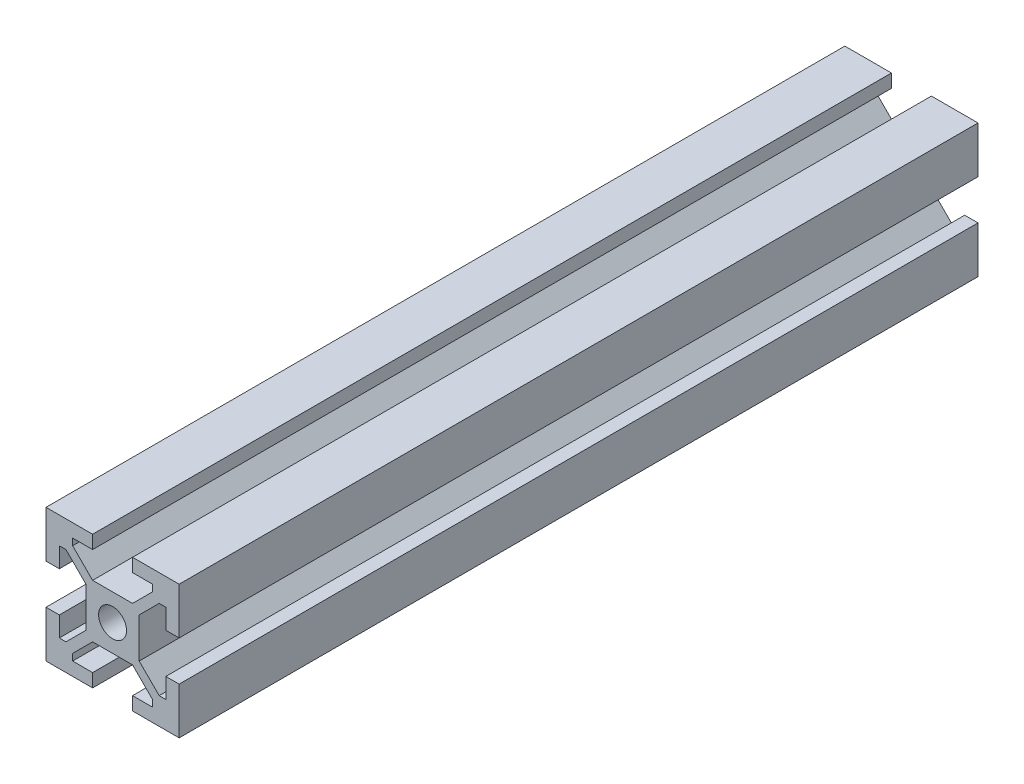
SolidWorks part; units mm, degrees
ref_plane "正面" through (0, 0, 0) normal (0, 0, 1) x (1, 0, 0)
ref_plane "平面" through (0, 0, 0) normal (0, 1, 0) x (1, 0, 0)
ref_plane "右側面" through (0, 0, 0) normal (1, 0, 0) x (0, 0, -1)
sketch "ｽｹｯﾁ2" plane through (0, 0, 0) normal (0, 0, 1) x (1, 0, 0)
  line L0 (0, 0) -> (0, 10) construction
  line L1 (-10, -10) -> (10, -10) construction
  line L2 (-10, -10) -> (-10, 10) construction
  line L3 (-10, 10) -> (10, 10) construction
  line L4 (10, -10) -> (10, 10) construction
  line L5 (-10, -10) -> (10, 10) construction
  line L6 (-10, 10) -> (10, -10) construction
  line L8 (3, 4) -> (-3, 4)
  line L9 (-6, 7) -> (6, 7) construction
  line L10 (-6, 8) -> (-6, 7)
  line L11 (6, 8) -> (6, 7)
  line L12 (-6, 7) -> (-3, 4)
  line L13 (3, 4) -> (6, 7)
  line L14 (-6, 8) -> (-3, 8)
  line L15 (-3, 8) -> (-3, 10)
  line L16 (-3, 10) -> (-10, 10)
  line L17 (6, 8) -> (3, 8)
  line L18 (3, 8) -> (3, 10)
  line L19 (3, 10) -> (10, 10)
  line L20 (7, 6) -> (4, 3)
  line L21 (4, -3) -> (4, 3)
  line L22 (4, -3) -> (7, -6)
  line L23 (8, -6) -> (8, -3)
  line L24 (8, -6) -> (7, -6)
  line L25 (8, -3) -> (10, -3)
  line L26 (10, -3) -> (10, -10)
  line L27 (8, 3) -> (10, 3)
  line L28 (10, 3) -> (10, 10)
  line L29 (8, 6) -> (8, 3)
  line L30 (8, 6) -> (7, 6)
  line L31 (6, -7) -> (3, -4)
  line L32 (-3, -4) -> (3, -4)
  line L33 (-3, -4) -> (-6, -7)
  line L34 (-6, -8) -> (-3, -8)
  line L35 (-6, -8) -> (-6, -7)
  line L36 (-3, -8) -> (-3, -10)
  line L37 (-3, -10) -> (-10, -10)
  line L38 (3, -8) -> (3, -10)
  line L39 (3, -10) -> (10, -10)
  line L40 (6, -8) -> (3, -8)
  line L41 (6, -8) -> (6, -7)
  line L42 (-7, -6) -> (-4, -3)
  line L43 (-4, 3) -> (-4, -3)
  line L44 (-4, 3) -> (-7, 6)
  line L45 (-8, 6) -> (-8, 3)
  line L46 (-8, 6) -> (-7, 6)
  line L47 (-8, 3) -> (-10, 3)
  line L48 (-10, 3) -> (-10, 10)
  line L49 (-8, -3) -> (-10, -3)
  line L50 (-10, -3) -> (-10, -10)
  line L51 (-8, -6) -> (-8, -3)
  line L52 (-8, -6) -> (-7, -6)
  circle A0 centre (0, 0) radius 2.1
  point P0 (0, 0)
  point P11 (0, 10)
  point P14 (0, 4)
  point P17 (0, 7)
  dimension "D8" = 4.2
  dimension "D1" = 20
  dimension "D2" = 6
  dimension "D3" = 2
  dimension "D4" = 4
  dimension "D5" = 12
  dimension "D6" = 6
  dimension "D7" = 4
extrude "ﾎﾞｽ - 押し出し1" add sketch "ｽｹｯﾁ2" along normal blind 120
